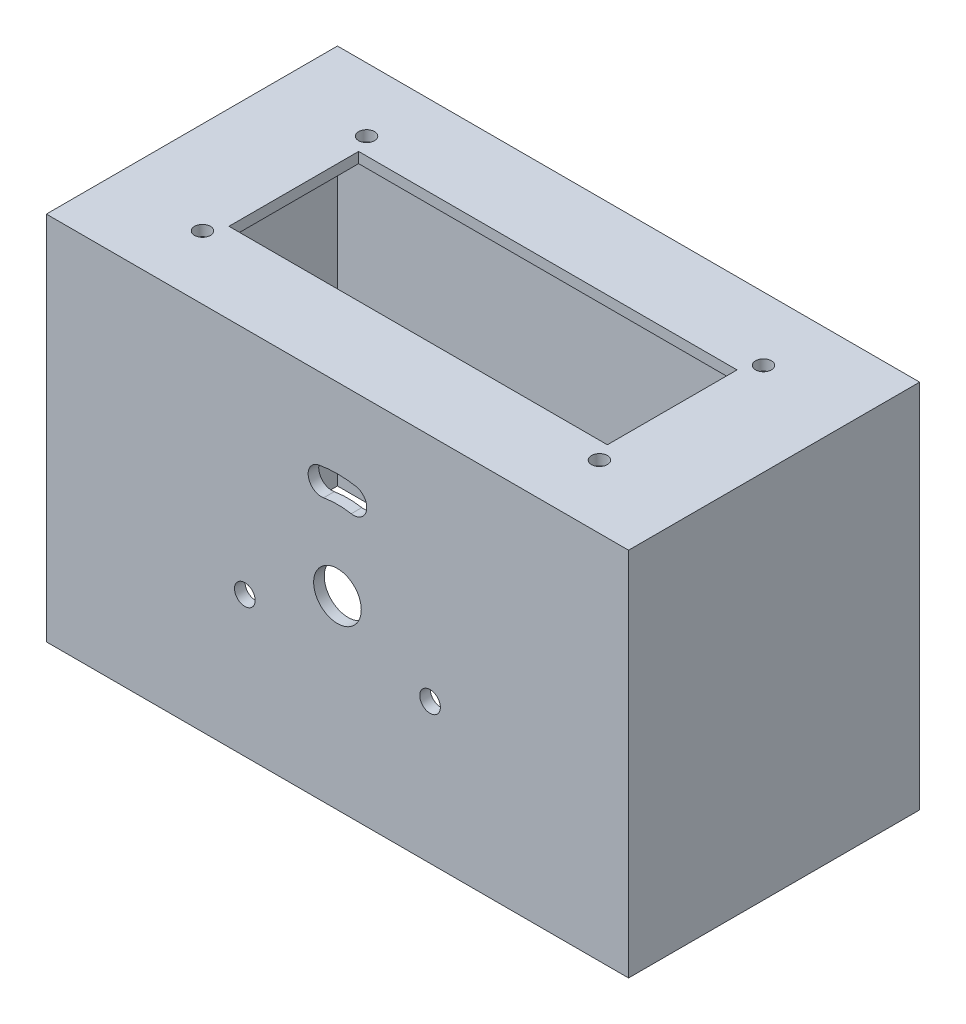
SolidWorks part; units mm, degrees
ref_plane "Front Plane" through (0, 0, 0) normal (0, 0, 1) x (1, 0, 0)
ref_plane "Top Plane" through (0, 0, 0) normal (0, 1, 0) x (1, 0, 0)
ref_plane "Right Plane" through (0, 0, 0) normal (1, 0, 0) x (0, 0, -1)
sketch "Sketch1" plane through (0, 0, 0) normal (0, 1, 0) x (1, 0, 0)
  line L0 (53, 25.5) -> (-53, 25.5)
  line L1 (55, -27.5) -> (-55, -27.5)
  line L2 (55, -27.5) -> (55, 27.5)
  line L3 (55, 27.5) -> (-55, 27.5)
  line L4 (-55, -27.5) -> (-55, 27.5)
  line L5 (55, -27.5) -> (-55, 27.5) construction
  line L6 (55, 27.5) -> (-55, -27.5) construction
  line L7 (-53, -25.5) -> (-53, 25.5)
  line L8 (53, -25.5) -> (-53, -25.5)
  line L9 (53, -25.5) -> (53, 25.5)
  line L10 (0, -6) -> (0, 0) construction
  line L11 (-14, -25.5) -> (14, -25.5)
  line L12 (-14, -25.5) -> (-14, -6) construction
  line L13 (-14, -6) -> (14, -6) construction
  line L14 (14, -25.5) -> (14, -6) construction
  line L15 (0, -25.5) -> (0, -27.5)
  line L16 (0, -27.5) -> (-4.5, -27.5)
  line L17 (-4.5, -27.5) -> (-4.5, -25.5)
  line L19 (35.75, -12.25) -> (-35.75, -12.25)
  line L20 (35.75, -12.25) -> (35.75, 12.25)
  line L21 (35.75, 12.25) -> (-35.75, 12.25)
  line L22 (-35.75, -12.25) -> (-35.75, 12.25)
  line L23 (35.75, -12.25) -> (-35.75, 12.25) construction
  line L24 (35.75, 12.25) -> (-35.75, -12.25) construction
  line L25 (37.5, -15.5) -> (-37.5, -15.5) construction
  line L26 (37.5, -15.5) -> (37.5, 15.5) construction
  line L27 (37.5, 15.5) -> (-37.5, 15.5) construction
  line L28 (-37.5, -15.5) -> (-37.5, 15.5) construction
  line L29 (37.5, -15.5) -> (-37.5, 15.5) construction
  line L30 (37.5, 15.5) -> (-37.5, -15.5) construction
  circle A0 centre (37.5, -15.5) radius 1.5
  circle A1 centre (37.5, 15.5) radius 1.5
  circle A2 centre (-37.5, 15.5) radius 1.5
  circle A3 centre (-37.5, -15.5) radius 1.5
  point P0 (0, 0)
  dimension "D10" = 3
  dimension "D1" = 2
  dimension "D2" = 55
  dimension "D3" = 110
  dimension "D4" = 19.5
  dimension "D5" = 28
  dimension "D6" = 2
  dimension "D7" = 4.5
  dimension "D8" = 71.5
  dimension "D9" = 24.5
  dimension "D11" = 75
  dimension "D12" = 31
extrude "Boss-Extrude1" add sketch "Sketch1" along normal mid plane 70 contours L1 L17 L8 L7 L0 L9 L15 L2 L3 L4 | L17 L1 L15 L11 region at (0, 0, -26.7298) region at (-2.25, 0, 26.5)
extrude "Boss-Extrude2" add sketch "Sketch1<3>" against normal blind 2 from surface contours L8 L9 L0 L7 L11 A3 A2 A1 A0 L19 L22 L21 L20 region at (51.8237, 0, 0) starting at face at (0, 35, 0)
sketch "Sketch1<3>" plane through (0, 0, 0) normal (0, 1, 0) x (1, 0, 0) same geometry as "Sketch1"
revolve "Cut-Revolve1" cut sketch "Sketch1<5>" angle 360 about L10 region at (-2.25, 0, 26.5)
sketch "Sketch1<5>" plane through (0, 0, 0) normal (0, 1, 0) x (1, 0, 0) same geometry as "Sketch1"
sketch "Sketch3" plane through (0, 0, 27.5) normal (0, 0, 1) x (1, 0, 0)
  line L0 (0, -8.5) -> (0, 5.5) construction
  line L1 (-21, -8.5) -> (21, -8.5) construction
  line L2 (17.5, -12) -> (-17.5, -12)
  line L3 (17.5, -12) -> (17.5, -5) construction
  line L4 (17.5, -5) -> (-17.5, -5)
  line L5 (-17.5, -12) -> (-17.5, -5) construction
  line L6 (17.5, -12) -> (-17.5, -5) construction
  line L7 (17.5, -5) -> (-17.5, -12) construction
  circle A0 centre (0, 0) radius 4.5 construction
  circle A1 centre (0, 0) radius 4.5
  circle A2 centre (0, -8.5) radius 14
  circle A3 centre (-17.5, -8.5) radius 3.5
  circle A4 centre (17.5, -8.5) radius 3.5
  circle A5 centre (-17.5, -8.5) radius 2
  circle A6 centre (17.5, -8.5) radius 2
  dimension "D1" = 28
  dimension "D4" = 7
  dimension "D5" = 4
  dimension "D2" = 5.5
  dimension "D3" = 42
extrude "Cut-Extrude1" cut sketch "Sketch3" against normal blind 2 contours A5 | A6 region at (-17.5, -8.5, 27.5) region at (17.5, -8.5, 27.5)
other "Move Face1" face at (19.5, -8.5, 25.5) face at (-15.5, -8.5, 25.5) offset 0.05 parameters "D1"=0.05
sketch "Sketch4" [suppressed] plane through (0, 0, 25.5) normal (0, 0, -1) x (-1, 0, 0)
  line L4 (0, -8.5) -> (-17.6777, 9.1777)
  line L5 (-17.6777, 9.1777) -> (0, -8.5)
  line L6 (0, -8.5) -> (17.6777, 9.1777)
  line L7 (17.6777, 9.1777) -> (0, -8.5)
  circle A1 centre (0, -8.5) radius 25
  arc A2 (8.5, -19.6243) -> (-8.5, -19.6243) centre (0, -8.5) ccw construction
  circle A3 centre (0, -8.5) radius 22
  arc A6 (17.6777, 9.1777) -> (15.5563, 7.0563) centre (16.617, 8.117) cw
  arc A7 (-17.6777, 9.1777) -> (-15.5563, 7.0563) centre (-16.617, 8.117) ccw
  point P6 (0, 0)
  point P18 (0, 0)
  point P19 (0, 0)
  dimension "D1" = 44
  dimension "D2" = 50
sketch "Sketch5" plane through (0, 0, 25.5) normal (0, 0, -1) x (-1, 0, 0)
  line L0 (0, 0) -> (3.473, 19.6962)
  line L1 (0, 0) -> (-3.473, 19.6962)
  circle A0 centre (0, 0) radius 20
  circle A1 centre (0, 0) radius 15
  arc A3 (3.473, 19.6962) -> (2.6047, 14.7721) centre (3.0388, 17.2341) cw
  arc A4 (-3.473, 19.6962) -> (-2.6047, 14.7721) centre (-3.0388, 17.2341) ccw
  point P10 (0, 0)
  point P11 (0, 0)
  dimension "D1" = 40
  dimension "D2" = 30
  dimension "D3" = 20
extrude "Cut-Extrude2" cut sketch "Sketch5" against normal through all contours A3 L0 | A1 L0 A0 L1 | L1 A4 region at (0, 17.5297, 25.5) region at (-4.0838, 17.0499, 25.5) region at (4.0838, 17.0499, 25.5)
